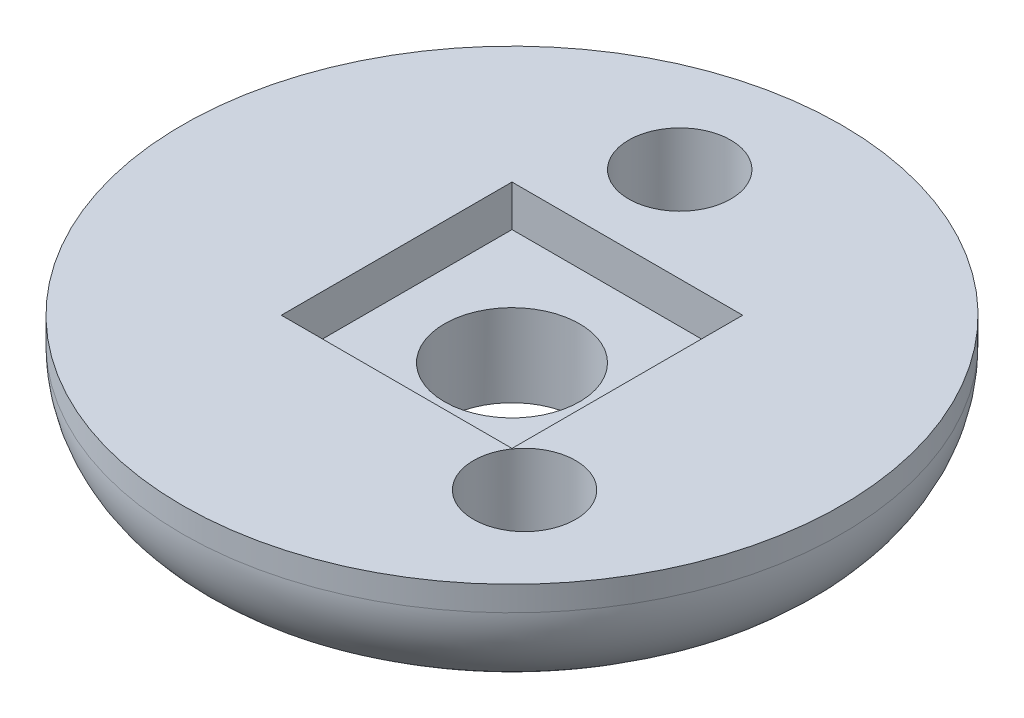
SolidWorks part; units mm, degrees
ref_plane "Front Plane" through (0, 0, 0) normal (0, 0, 1) x (1, 0, 0)
ref_plane "Top Plane" through (0, 0, 0) normal (0, 1, 0) x (1, 0, 0)
ref_plane "Right Plane" through (0, 0, 0) normal (1, 0, 0) x (0, 0, -1)
sketch "Sketch1" plane through (0, 0, 0) normal (0, 1, 0) x (1, 0, 0)
  circle A0 centre (0, 0) radius 10
  dimension "D1" = 20
extrude "Boss-Extrude1" add sketch "Sketch1" along normal blind 3 and the other way blind 10
ref_axis "5hubaxis" through (0, 5.5, 0) along (0, -1, 0)
ref_plane "holeplane" through (-3.3529, -1.0931, 1.8877) normal (0.8382, 0.2733, -0.4719) x (-0.4487, -0.1463, -0.8816)
sketch "Sketch4" plane through (-3.3529, -1.0931, 1.8877) normal (0.8382, 0.2733, -0.4719) x (-0.4487, -0.1463, -0.8816)
  circle A0 centre (0, 0) radius 1.5 construction
  circle A1 centre (0, 0) radius 1.5
extrude "hole" cut sketch "Sketch4" against normal through all
pattern_circular "holecir" count 5 over 360 about axis through (0, 5.5, 0) along (0, -1, 0) of "hole"
sketch "Sketch5" plane through (0, -10, 0) normal (0, -1, 0) x (1, 0, 0)
  line L0 (-10, 0) -> (10, 0) construction
  circle A0 centre (0, 0) radius 10 construction
  text T0 "5"
extrude "Boss-Extrude2" [suppressed] add sketch "Sketch5" along normal blind 1
ref_plane "Plane1" through (0, -5, 0) normal (0, -1, 0) x (-1, 0, 0)
sketch "Sketch6" plane through (0, -5, 0) normal (0, -1, 0) x (-1, 0, 0)
  line L1 (3.5, 3.5) -> (-3.5, 3.5)
  line L2 (3.5, 3.5) -> (3.5, -3.5)
  line L3 (3.5, -3.5) -> (-3.5, -3.5)
  line L4 (-3.5, 3.5) -> (-3.5, -3.5)
  line L5 (3.5, 3.5) -> (-3.5, -3.5) construction
  line L6 (3.5, -3.5) -> (-3.5, 3.5) construction
  point P0 (0, 0)
  dimension "D1" = 7
  dimension "D2" = 7
extrude "bearinghole" cut sketch "Sketch6" along normal blind 2.5
sketch "Sketch7" plane through (0, -5, 0) normal (0, -1, 0) x (-1, 0, 0)
  circle A0 centre (0, 0) radius 2.05
  dimension "D1" = 4.1
extrude "shafthole" cut sketch "Sketch7" along normal through all
sketch "Sketch8" plane through (0, 3, 0) normal (0, 1, 0) x (1, 0, 0)
  line L0 (-1.9732, 9.8034) -> (0, 0) construction
  line L1 (0, 0) -> (7.3586, -6.7713) construction
  line L2 (0, 0) -> (1.9732, -9.8034) construction
  line L3 (3.4214, -9.3965) -> (2.2297, -3.4761) construction
  line L4 (0, 0) -> (9.9333, -1.1528) construction
  line L5 (9.9939, 0.3502) -> (3.995, 1.0464) construction
  line L6 (0, 0) -> (4.166, 9.0909) construction
  line L7 (2.7552, 9.613) -> (0.2393, 4.1229) construction
  circle A0 centre (0, 0) radius 10 construction
  circle A1 centre (0, 0) radius 6.5 construction
  point P15 (-1.2826, 6.3722)
  point P16 (4.7831, -4.4014)
  dimension "D3" = 13
  dimension "D1" = 36
  dimension "D2" = 36
hole_wizard "Ø3.1 (3.1) Diameter Hole1" positions "Sketch9" profile "Sketch10" hole size "Ø3.1" standard "ISO" end condition through all
sketch "Sketch9" plane through (0, 3, 0) normal (0, 1, 0) x (1, 0, 0)
  point P0 (-1.2826, 6.3722)
  point P3 (4.7831, -4.4014)
sketch "Sketch10" plane through (-1.2826, 3, -6.3722) normal (1, 0, 0) x (0, 0, 1)
  line L0 (0, 0) -> (0, 13)
  line L1 (0, 13) -> (1.55, 13)
  line L2 (1.55, 13) -> (1.55, 0)
  line L5 (1.55, 0) -> (0, 0)
  line L11 (0, -6.35) -> (0, 107.95) construction
  dimension "Thru Hole Dia." = 3.1
  dimension "Thru Hole Depth" = 13
fillet "Fillet2" radius 3 2 edges at (0, 3, 10) (0, -10, 10)
ref_plane "Plane2" through (0, -6.25, 0) normal (0, -1, 0) x (-1, 0, 0)
sketch "Sketch11" plane through (0, -6.25, 0) normal (0, -1, 0) x (-1, 0, 0)
  circle A0 centre (0, 0) radius 10
extrude "Cut-Extrude1" cut sketch "Sketch11" against normal blind 10
